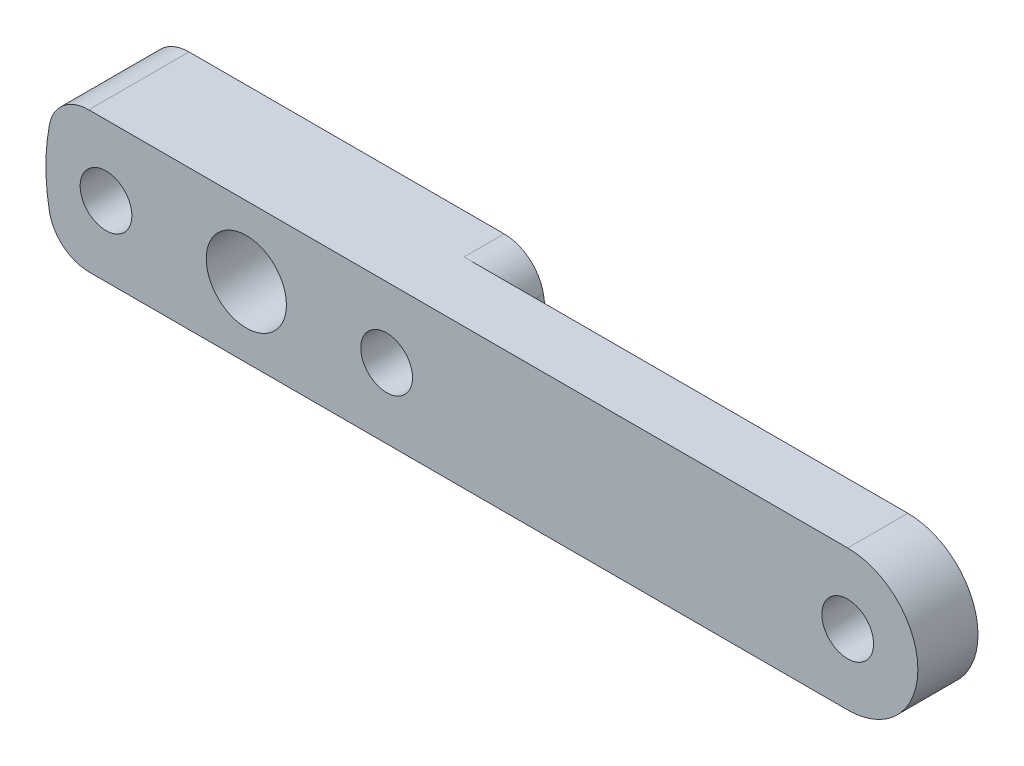
SolidWorks part; units mm, degrees
ref_plane "Front Plane" through (0, 0, 0) normal (0, 0, 1) x (1, 0, 0)
ref_plane "Top Plane" through (0, 0, 0) normal (0, 1, 0) x (1, 0, 0)
ref_plane "Right Plane" through (0, 0, 0) normal (1, 0, 0) x (0, 0, -1)
sketch "Sketch1" plane through (0, 0, 0) normal (0, 0, 1) x (1, 0, 0)
  line L0 (-9.3675, 3.5) -> (30, 3.5)
  line L1 (30, -3.5) -> (-9.3675, -3.5)
  line L2 (-7, 0) -> (7, 0) construction
  arc A0 (-9.3675, -3.5) -> (-9.3675, 3.5) centre (0, 0) cw
  arc A1 (30, 3.5) -> (30, -3.5) centre (30, 0) cw
  circle A2 centre (-7, 0) radius 1.29
  circle A3 centre (7, 0) radius 1.29
  circle A4 centre (30, 0) radius 1.29
  circle A5 centre (0, 0) radius 2
  point P6 (-10, 0)
  point P12 (0, 0)
  dimension "D1" = 10
  dimension "D2" = 7
  dimension "D4" = 2.58
  dimension "D6" = 4
  dimension "D3" = 30
  dimension "D5" = 14
extrude "Boss-Extrude1" add sketch "Sketch1" along normal mid plane 5
sketch "Sketch2" plane through (0, 0, -2.5) normal (0, 0, -1) x (-1, 0, 0)
  line L0 (9.3675, -3.5) -> (-30, -3.5) construction
  line L1 (-30, 3.5) -> (9.3675, 3.5) construction
  line L2 (-30, 3.5) -> (-9.3675, 3.5)
  line L3 (-9.3675, -3.5) -> (-30, -3.5)
  arc A0 (-30, 3.5) -> (-30, -3.5) centre (-30, 0) ccw construction
  arc A1 (-30, 3.5) -> (-30, -3.5) centre (-30, 0) ccw
  arc A2 (-9.3675, -3.5) -> (-9.3675, 3.5) centre (0, 0) cw
  point P4 (0, 0)
  dimension "D1" = 10
extrude "Cut-Extrude1" cut sketch "Sketch2" against normal offset from surface (2 mm away) 3 up to face at (11.0331, 0, 2.5)
fillet "Fillet1" radius 2 4 edges at (-9.3675, -3.5, 0) (-9.3675, 3.5, 0) (9.3675, -3.5, -1.5) (9.3675, 3.5, -1.5)
sketch "Sketch3" plane through (0, 0, -2.5) normal (0, 0, -1) x (-1, 0, 0)
  point P0 (0, 0)
